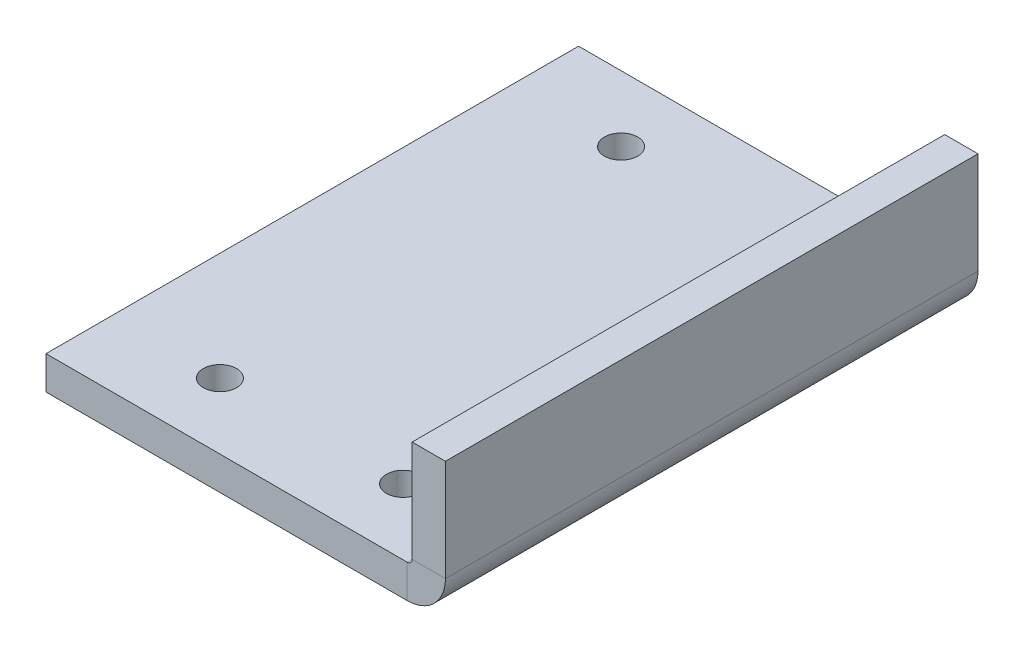
SolidWorks part; units mm, degrees
note: The reader was unsure of these and kept them because the rebuilt part matched: thickness of "Brida base1", "Brida de arista1", "Chapa metálica1", "Chapa metálica2", "Chapa metálica3"; flange length of "Brida de arista1".
material "1060-H16"
ref_plane "Alzado" through (0, 0, 0) normal (0, 0, 1) x (1, 0, 0)
ref_plane "Planta" through (0, 0, 0) normal (0, 1, 0) x (1, 0, 0)
ref_plane "Vista lateral" through (0, 0, 0) normal (1, 0, 0) x (0, 0, -1)
sketch "Croquis1" plane through (0, 0, 0) normal (0, 1, 0) x (1, 0, 0)
  line L1 (-30, -40) -> (30, -40)
  line L2 (-30, -40) -> (-30, 40)
  line L3 (-30, 40) -> (30, 40)
  line L4 (30, -40) -> (30, 40)
  line L5 (-30, -40) -> (30, 40) construction
  line L6 (-30, 40) -> (30, -40) construction
  point P0 (0, 0)
  dimension "D1" = 60
  dimension "D2" = 80
base flange "Brida base1" sketch "Croquis1" thickness 5 reverse thickness direction no parameters "D1"=0.7366
edge flange "Brida de arista1" sketch "Croquis8" flange angle 90 flange length 21 flange position material inside bend radius 0.7366 thickness 5 relief rectangular parameters "D6"=10
sketch "Croquis8" plane through (30, 0, 0) normal (1, 0, 0) x (0, 0, -1)
  line L0 (-40, 0) -> (40, 0) construction
  line L1 (-40, 0) -> (40, 0)
  line L2 (-40, 0) -> (-40, 16)
  line L3 (-40, 16) -> (40, 16)
  line L4 (40, 16) -> (40, 0)
bend "Pliegue de arista1" bend radius 0.7366 bend angle 90 parameters "D5"=1
sketch "Croquis9" plane through (0, 0, 0) normal (0, 1, 0) x (1, 0, 0)
  line L0 (-30, 40) -> (-30, -40) construction
  line L1 (-13.75, -30.12) -> (13.75, -30.12) construction
  line L2 (-13.75, -30.12) -> (-13.75, 30.13) construction
  line L3 (-13.75, 30.13) -> (13.75, 30.13) construction
  line L4 (13.75, -30.12) -> (13.75, 30.13) construction
  line L5 (-13.75, -30.12) -> (13.75, 30.13) construction
  line L6 (-13.75, 30.13) -> (13.75, -30.12) construction
  line L7 (-30, -40) -> (24.2634, -40) construction
  circle A0 centre (-13.75, 30.13) radius 2.5
  circle A1 centre (13.75, 30.13) radius 2.5
  circle A2 centre (13.75, -30.12) radius 2.5
  circle A3 centre (-13.75, -30.12) radius 2.5
  point P0 (0, 0.005)
  dimension "D5" = 5
  dimension "D1" = 27.5
  dimension "D2" = 60.25
  dimension "D3" = 16.25
  dimension "D4" = 9.88
extrude "Cortar-Extruir1" cut sketch "Croquis9" against normal up to surface (5 mm away) normal cut yes up to face at (-2.8683, -5, 0)
sketch "Líneas de pliegue1" [suppressed] plane through (0, 0, 0) normal (0, 1, 0) x (1, 0, 0)
sketch "Cuadro delimitador1" [suppressed] plane through (0, 0, 0) normal (0, 1, 0) x (1, 0, 0)
sheet metal parameters "Chapa metálica1" thickness 5 parameters "D1"=0.7366
flat pattern "Chapa desplegada1" [suppressed]
sketch "Líneas de pliegue2" plane through (0, 0, 0) normal (0, 1, 0) x (1, 0, 0)
sketch3d "Cuadro delimitador2" [suppressed]
  line L0 (30, -40, 0) -> (30, 40, 0) construction
  line L1 (-30, -40, 0) -> (-30, 40, 0) construction
  line L2 (30, -40, 0) -> (-30, -40, 0) construction
  line L3 (30, 40, 0) -> (-30, 40, 0) construction
sheet metal parameters "Chapa metálica2" thickness 5 parameters "D1"=0.7366, "D7"=2
flat pattern "Chapa desplegada1"
sketch "Líneas de pliegue2" plane through (0, 0, 0) normal (0, 1, 0) x (1, 0, 0)
  line L0 (28.6273, -40) -> (28.6273, 40) construction
  line L1 (28.6273, -40) -> (28.6273, 40) construction
sketch3d "Cuadro delimitador2" [suppressed]
  line L0 (-30, -40, 0) -> (-30, 40, 0) construction
  line L1 (48.2546, -40, 0) -> (48.2546, 40, 0) construction
  line L2 (-30, -40, 0) -> (48.2546, -40, 0) construction
  line L3 (-30, 40, 0) -> (48.2546, 40, 0) construction
bend of the flat pattern "Aplanar-<Pliegue de arista1>1"
sheet metal parameters "Chapa metálica3" thickness 5 parameters "D1"=0.7366, "D7"=2
flat pattern "Chapa desplegada1"
sketch "Líneas de pliegue2" plane through (0, 0, 0) normal (0, 1, 0) x (1, 0, 0)
  line L0 (26.8054, -40) -> (26.8054, 40) construction
  line L1 (26.8054, -40) -> (26.8054, 40) construction
sketch3d "Cuadro delimitador2" [suppressed]
  line L0 (-30, -40, 0) -> (-30, 40, 0) construction
  line L1 (44.6108, -40, 0) -> (44.6108, 40, 0) construction
  line L2 (-30, -40, 0) -> (44.6108, -40, 0) construction
  line L3 (-30, 40, 0) -> (44.6108, 40, 0) construction
bend of the flat pattern "Aplanar-<Pliegue de arista1>1"
